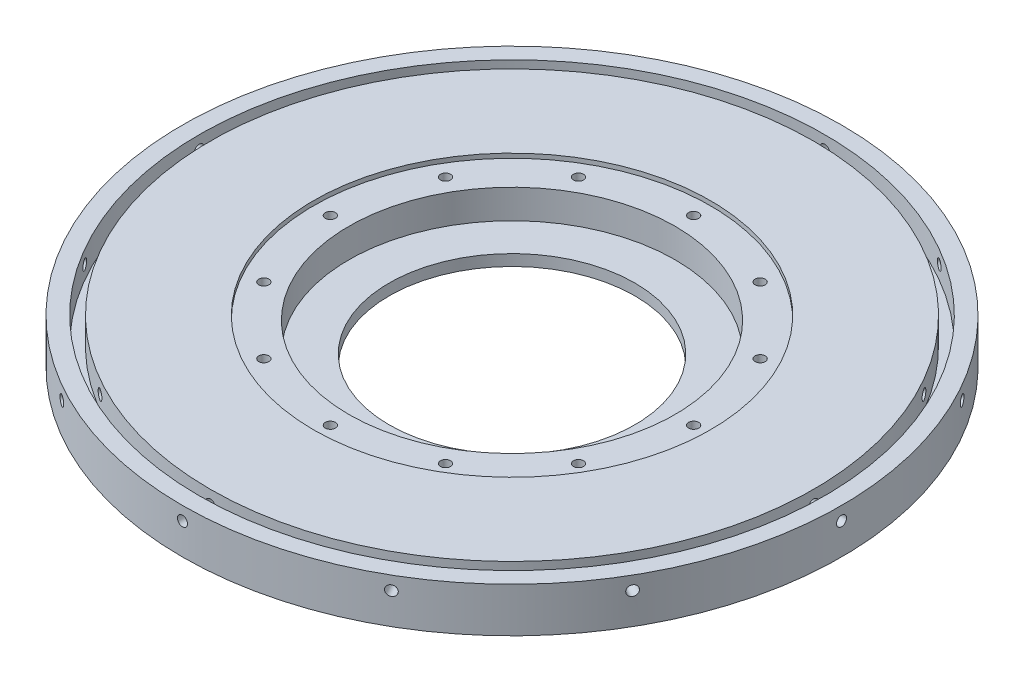
SolidWorks part; units mm, degrees
material "6061-T6 (SS)"
ref_plane "Front Plane" through (0, 0, 0) normal (0, 0, 1) x (1, 0, 0)
ref_plane "Top Plane" through (0, 0, 0) normal (0, 1, 0) x (1, 0, 0)
ref_plane "Right Plane" through (0, 0, 0) normal (1, 0, 0) x (0, 0, -1)
sketch "Sketch1" plane through (0, 0, 0) normal (0, 1, 0) x (1, 0, 0)
  line L5 (0, 0) -> (127.635, 0)
  line L6 (0, 0) -> (0, 127.635)
  line L7 (0, 127.635) -> (127.635, 127.635)
  line L8 (127.635, 0) -> (127.635, 127.635)
  dimension "D1" = 127.635
  dimension "D2" = 127.635
extrude "Boss-Extrude1" add sketch "Sketch1" along normal blind 9.525 contours L5 L8 L7 L6
sketch "Sketch13" plane through (0, 9.525, 0) normal (0, 1, 0) x (1, 0, 0)
  circle A0 centre (63.8175, 63.8175) radius 93.6625
  dimension "D1" = 187.325
extrude "Boss-Extrude2" add sketch "Sketch13" against normal blind 12.7 contours A0
sketch "Sketch6" [suppressed] plane through (127.635, 0, 0) normal (1, 0, 0) x (0, 0, -1)
  circle A0 centre (4.7625, 4.7625) radius 1.3526
  dimension "D1" = 2.7051
extrude "6-32 hole1" [suppressed] cut sketch "Sketch6" against normal blind 12.7
sketch "Sketch7" [suppressed] plane through (0, 0, -127.635) normal (0, 0, -1) x (-1, 0, 0)
  circle A0 centre (-122.8725, 4.7625) radius 1.3525
  dimension "D1" = 2.7051
sketch "Sketch8" [suppressed] plane through (0, 0, 0) normal (-1, 0, 0) x (0, 0, 1)
  circle A0 centre (-122.8725, 4.7625) radius 1.3525
  dimension "D1" = 2.7051
sketch "Sketch9" [suppressed] plane through (0, 0, 0) normal (0, 0, 1) x (1, 0, 0)
  circle A0 centre (4.7625, 4.7625) radius 1.3526
  dimension "D1" = 2.7051
sketch "Sketch5" plane through (0, 9.525, 0) normal (0, 1, 0) x (1, 0, 0)
  circle A0 centre (63.8175, 63.8175) radius 46.355
  circle A1 centre (63.8175, 63.8175) radius 93.6625 construction
  dimension "D1" = 92.71
extrude "Cut-Extrude1" cut sketch "Sketch5" against normal blind 9.525
sketch "Sketch11" plane through (0, 9.525, 0) normal (0, 1, 0) x (1, 0, 0)
  line L0 (63.8175, 63.8175) -> (63.8175, 115.443) construction
  circle A0 centre (63.8175, 115.443) radius 1.4351
  dimension "D2" = 2.8702
  dimension "D1" = 51.6255
extrude "Cut-Extrude3" cut sketch "Sketch11" against normal through all contours A0
pattern_circular "CirPattern1" count 12 over 360 about axis through (63.8175, 9.525, -63.8175) along (0, 1, 0) of "Cut-Extrude3"
sketch "Sketch12" plane through (0, 9.525, 0) normal (0, 1, 0) x (1, 0, 0)
  circle A0 centre (63.8175, 63.8175) radius 56.4198
  dimension "D1" = 112.8395
extrude "Cut-Extrude4" cut sketch "Sketch12" against normal blind 1.27
sketch "Sketch15" plane through (0, 9.525, 0) normal (0, 1, 0) x (1, 0, 0)
  line L0 (63.8175, 63.8175) -> (-29.845, 63.8175) construction
  line L1 (0, -39.1057) -> (0, 39.1057) construction
  line L2 (-20.0025, 63.8175) -> (-25.0825, 63.8175)
  line L3 (-8.7458, 105.7742) -> (-13.2051, 108.2104)
  line L4 (-8.7458, 105.7742) -> (-20.0025, 63.8175) construction
  circle A0 centre (63.8175, 63.8175) radius 56.4198 construction
  arc A1 (-20.0025, 63.8175) -> (-8.7458, 105.7742) centre (63.8175, 63.8175) cw
  arc A2 (-25.0825, 63.8175) -> (-13.2051, 108.2104) centre (63.8175, 63.8175) cw
  circle A3 centre (63.8175, 63.8175) radius 93.6625 construction
  point P0 (63.8175, 63.8175)
  point P11 (-14.3741, 84.7959)
  dimension "D1" = 46.482
  dimension "D2" = 88.9
  dimension "D3" = 83.82
  dimension "D4" = 43.942
sketch "Sketch16" plane through (0, 9.525, 0) normal (0, 1, 0) x (1, 0, 0)
  circle A0 centre (63.8175, 63.8175) radius 88.9
  circle A1 centre (63.8175, 63.8175) radius 85.725
  dimension "D1" = 177.8
  dimension "D2" = 171.45
extrude "Cut-Extrude5" cut sketch "Sketch16" against normal blind 7.62
sketch "Sketch18" plane through (0, 8.255, 0) normal (0, 1, 0) x (1, 0, 0)
  line L0 (63.8175, 185.7252) -> (63.8175, -48.6103) construction
ref_plane "Plane1" through (63.8175, 0, 0) normal (-1, 0, 0) x (0, 0, 1)
ref_plane "Plane2" through (0, 0, 29.845) normal (0, 0, 1) x (1, 0, 0)
sketch "Sketch17" plane through (0, 0, 29.845) normal (0, 0, 1) x (1, 0, 0)
  line L0 (63.8175, 103.0287) -> (63.8175, -103.0287) construction
  line L1 (157.48, 9.525) -> (-29.845, 9.525) construction
  circle A0 centre (63.8175, 5.715) radius 1.4351
  dimension "D1" = 2.8702
  dimension "D2" = 3.81
extrude "Cut-Extrude6" cut sketch "Sketch17" against normal blind 15.24
pattern_circular "CirPattern2" count 12 over 360 about axis through (63.8175, -3.175, -63.8175) along (0, 1, 0) of "Cut-Extrude6" reverse direction yes
sketch "Sketch19" plane through (0, -3.175, 0) normal (0, -1, 0) x (1, 0, 0)
  circle A0 centre (63.8175, -63.8175) radius 34.925
  dimension "D1" = 69.85
extrude "Cut-Extrude7" cut sketch "Sketch19" against normal blind 87.63
